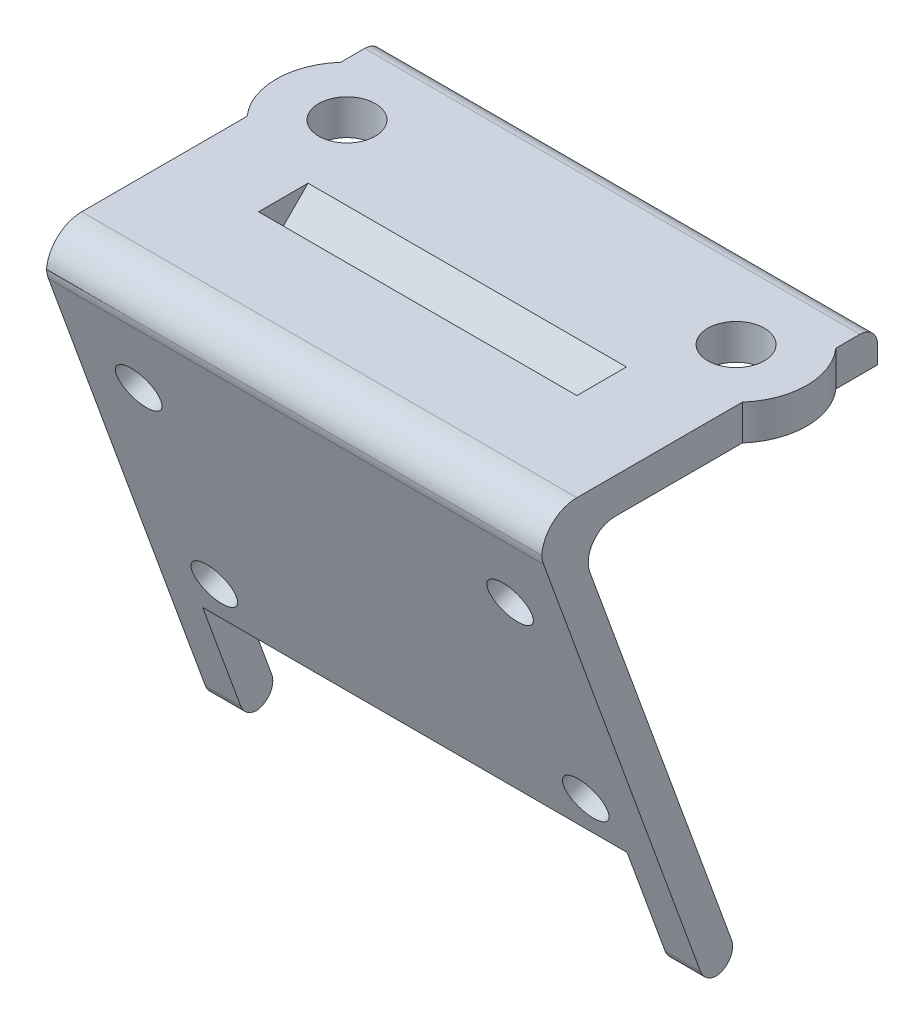
SolidWorks part; units mm, degrees
ref_plane "Płaszczyzna przednia" through (0, 0, 0) normal (0, 0, 1) x (1, 0, 0)
ref_plane "Płaszczyzna górna" through (0, 0, 0) normal (0, 1, 0) x (1, 0, 0)
ref_plane "Płaszczyzna prawa" through (0, 0, 0) normal (1, 0, 0) x (0, 0, -1)
sketch "Szkic1" plane through (0, 0, 0) normal (0, 1, 0) x (1, 0, 0)
  line L1 (-14, -9.5) -> (14, -9.5)
  line L2 (-14, -9.5) -> (-14, 9.5)
  line L3 (-14, 9.5) -> (14, 9.5)
  line L4 (14, -9.5) -> (14, 9.5)
  line L5 (-14, -9.5) -> (14, 9.5) construction
  line L6 (-14, 9.5) -> (14, -9.5) construction
  point P0 (0, 0)
  dimension "D1" = 19
  dimension "D2" = 28
extrude "Dodanie-wyciągnięcie1" add sketch "Szkic1" along normal blind 2
sketch "Szkic2" plane through (0, 2, 0) normal (0, 1, 0) x (1, 0, 0)
  line L0 (0, 0) -> (0, 4.5) construction
  line L1 (-11, 4.5) -> (11, 4.5) construction
  line L2 (14, 9.5) -> (-14, 9.5) construction
  circle A0 centre (11, 4.5) radius 1.6
  circle A1 centre (-11, 4.5) radius 1.6
  point P6 (0, 4.5)
  dimension "D2" = 3.2
  dimension "D1" = 22
  dimension "D3" = 5
extrude "Wytnij-wyciągnięcie1" cut sketch "Szkic2" against normal through all
sketch "Szkic7" plane through (0, 2, 0) normal (0, 1, 0) x (1, 0, 0)
  circle A1 centre (11, 4.5) radius 4
  circle A2 centre (11, 4.5) radius 1.6
  dimension "D1" = 8
extrude "Dodanie-wyciągnięcie3" add sketch "Szkic7" against normal up to surface (2 mm away) up to face at (11, 0, -2.9)
mirror "Lustro1" about plane through (0, 0, 0) normal (1, 0, 0) of "Dodanie-wyciągnięcie3"
sketch "Szkic3" plane through (14, 0, 0) normal (1, 0, 0) x (0, 0, -1)
  line L0 (-9.5, 2) -> (-9.5, 0) construction
  line L1 (-9.5, 0) -> (-0.2655, -25.3717)
  line L2 (-0.2655, -25.3717) -> (1.7345, -25.3717)
  line L3 (1.7345, -25.3717) -> (-7.5, 0)
  line L4 (-9.5, 0) -> (1.8542, 0) construction
  line L5 (-7.5, 0) -> (-9.5, 0)
  dimension "D1" = 20
  dimension "D2" = 2
  dimension "D3" = 2
  dimension "D4" = 27
extrude "Dodanie-wyciągnięcie2" add sketch "Szkic3" against normal up to surface (28 mm away) up to face at (-14, 1, -8.3229)
sketch "Szkic4" plane through (0, -3.0532, 8.3887) normal (0, -0.342, 0.9397) x (1, 0, 0)
  line L0 (0, 3.2492) -> (0, -1.7875) construction
  line L1 (-14, 3.2492) -> (14, 3.2492) construction
  line L2 (-10.5, -1.7875) -> (10.5, -1.7875) construction
  line L3 (-10.5, -1.7875) -> (-10.5, -14.2875) construction
  circle A0 centre (-10.5, -1.7875) radius 1.25
  circle A1 centre (-10.5, -14.2875) radius 1.25
  circle A2 centre (10.5, -14.2875) radius 1.25
  circle A3 centre (10.5, -1.7875) radius 1.25
  point P8 (0, -1.7875)
  dimension "D2" = 2.5
  dimension "D4" = 2.5
  dimension "D1" = 21
  dimension "D3" = 12.5
extrude "Wytnij-wyciągnięcie2" cut sketch "Szkic4" against normal up to surface (1.8794 mm away) up to face at (0, -12.6859, 2.8827)
sketch "Szkic6" plane through (0, -3.0532, 8.3887) normal (0, -0.342, 0.9397) x (1, 0, 0)
  line L0 (-14, -23.7508) -> (14, -23.7508) construction
  line L1 (-12, -23.7508) -> (12, -23.7508) construction
  line L2 (-12, -23.7508) -> (-12, -16.7508)
  line L3 (-12, -16.7508) -> (12, -16.7508)
  line L4 (12, -23.7508) -> (12, -16.7508)
  line L5 (-12, -23.7508) -> (12, -16.7508) construction
  line L6 (-12, -16.7508) -> (12, -23.7508) construction
  line L7 (-12, -23.7508) -> (-12, -25.9094)
  line L8 (-12, -25.9094) -> (12, -25.9094)
  line L9 (12, -25.9094) -> (12, -23.7508)
  point P4 (0, -20.2508)
  point P7 (0, -23.7508)
  point P8 (0, -23.7508)
  dimension "D1" = 24
  dimension "D2" = 7
extrude "Wytnij-wyciągnięcie4" cut sketch "Szkic6" against normal through all
fillet "Zaokrąglenie1" radius 2 2 edges at (0, 2, 9.5) (0, 0, 9.5)
fillet "Zaokrąglenie2" radius 1.5 1 edges at (0, 0, 7.5)
fillet "Zaokrąglenie3" radius 1 4 edges at (13, -25.3717, -1.7345) (-13, -25.3717, -1.7345) (-13, -25.3717, 0.2655) (13, -25.3717, 0.2655)
fillet "Zaokrąglenie4" radius 1 1 edges at (0, 2, -9.5)
sketch "Szkic9" plane through (0, 2, 0) normal (0, 1, 0) x (1, 0, 0)
  line L0 (0, 0) -> (0, -2) construction
  line L2 (-9, -1.5) -> (9, -1.5)
  line L3 (-9, -1.5) -> (-9, -2.5)
  line L4 (-9, -2.5) -> (9, -2.5)
  line L5 (9, -1.5) -> (9, -2.5)
  line L6 (-9, -1.5) -> (9, -2.5) construction
  line L7 (-9, -2.5) -> (9, -1.5) construction
  point P6 (0, 0)
  point P7 (0, 0)
  point P8 (0, 0)
  point P9 (0, 0)
  dimension "D1" = 2
  dimension "D2" = 1
  dimension "D3" = 18
extrude "Wytnij-wyciągnięcie5" cut sketch "Szkic9" against normal up to surface (2 mm away) contours L2 L5 L4 L3 up to face at (0, 0, -3.2856)
chamfer "Sfazowanie1" distance 1.8 angle 45 2 edges at (0, 2, 1.5) (0, 0, 2.5)
